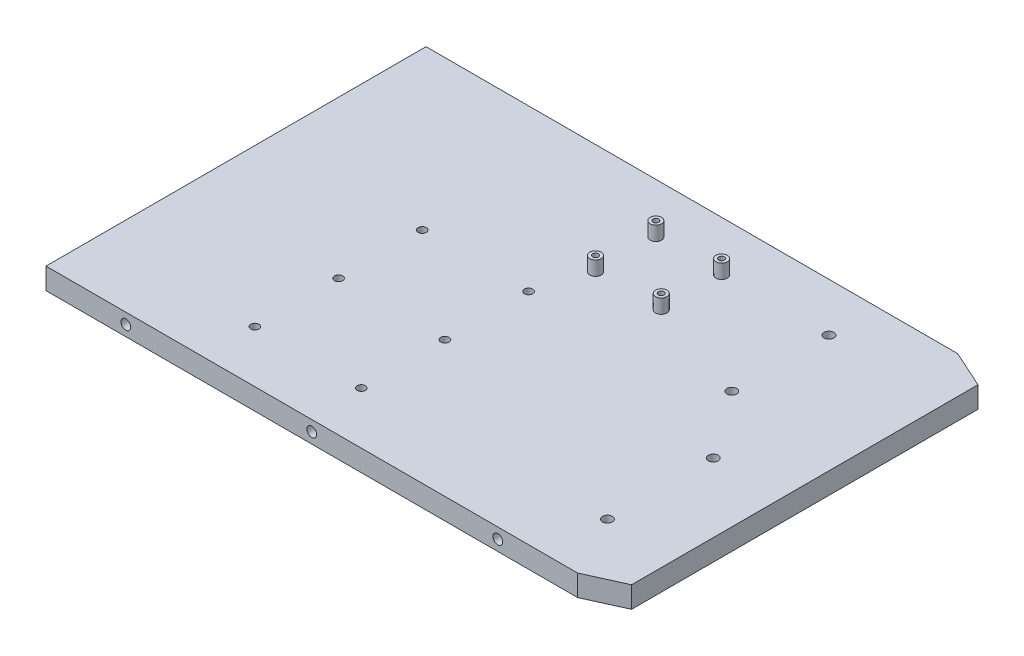
SolidWorks part; units mm, degrees
ref_plane "Front Plane" through (0, 0, 0) normal (0, 0, 1) x (1, 0, 0)
ref_plane "Top Plane" through (0, 0, 0) normal (0, 1, 0) x (1, 0, 0)
ref_plane "Right Plane" through (0, 0, 0) normal (1, 0, 0) x (0, 0, -1)
sketch "Sketch1" plane through (0, 0, 0) normal (0, 1, 0) x (1, 0, 0)
  line L2 (0, 12.0331) -> (0, 268.5969)
  line L6 (374.81, 274.2969) -> (374.81, 268.5969)
  line L9 (401.01, 18.185) -> (401.01, 262.445)
  line L10 (401.01, 262.445) -> (374.81, 274.2969)
  line L12 (374.81, 268.5969) -> (0, 268.5969)
  line L13 (0, 140.315) -> (401.01, 140.315) construction
  line L15 (401.01, 18.185) -> (374.81, 6.3331)
  line L17 (374.81, 12.0331) -> (0, 12.0331)
  line L18 (374.81, 6.3331) -> (374.81, 12.0331)
extrude "Boss-Extrude1" add sketch "Sketch1" along normal blind 10
sketch "Sketch2" plane through (0, 10, 0) normal (0, 1, 0) x (1, 0, 0)
  line L0 (0, 268.5969) -> (0, 12.0331)
  line L1 (352.4341, 121.6803) -> (352.4341, 127.0803) construction
  line L2 (0, 12.0331) -> (374.81, 12.0331)
  line L3 (352.4341, 52.4303) -> (352.4341, 47.0303) construction
  line L4 (374.81, 12.0331) -> (374.81, 6.3331)
  line L5 (374.81, 6.3331) -> (401.01, 18.185)
  line L6 (401.01, 18.185) -> (401.01, 262.445)
  line L7 (401.01, 262.445) -> (374.81, 274.2969)
  line L8 (374.81, 274.2969) -> (374.81, 268.5969)
  line L9 (374.81, 268.5969) -> (0, 268.5969)
  circle A0 centre (185.5985, 102.0168) radius 2.925
  circle A1 centre (185.5985, 161.0168) radius 2.925
  circle A2 centre (185.5985, 43.0168) radius 2.925
  circle A3 centre (110.5985, 43.0168) radius 2.925
  circle A4 centre (110.5985, 102.0168) radius 2.925
  circle A5 centre (110.5985, 161.0168) radius 2.925
  circle A8 centre (352.4341, 124.3803) radius 3.455
  circle A9 centre (352.4341, 49.7303) radius 3.455
  circle A10 centre (318.1841, 240.1847) radius 3.45
  circle A11 centre (318.1841, 171.6847) radius 3.45
  line M1 (0, 268.5969) -> (0, 12.0331)
extrude "Boss-Extrude3" add sketch "Sketch2" along normal blind 5 contours A4 A3 A0 A1 A2 A5 M1 region at (200.3556, 10, -140.3663)
sketch "Sketch3" plane through (0, 15, 0) normal (0, 1, 0) x (1, 0, 0)
  circle A0 centre (197.1863, 196.582) radius 2
  circle A1 centre (243.5413, 196.582) radius 2
  circle A2 centre (243.5413, 239.127) radius 2
  circle A3 centre (197.1863, 239.127) radius 2
  circle A4 centre (197.1863, 196.582) radius 4
  circle A5 centre (197.1863, 239.127) radius 4
  circle A6 centre (243.5413, 239.127) radius 4
  circle A8 centre (243.5413, 196.582) radius 4
extrude "Boss-Extrude4" add sketch "Sketch3" along normal blind 10
sketch "Sketch4" plane through (0, 0, -12.0331) normal (0, 0, 1) x (1, 0, 0)
  line L1 (0, 0) -> (374.81, 0)
  line L2 (0, 0) -> (0, 15)
  line L3 (0, 15) -> (374.81, 15)
  line L4 (374.81, 0) -> (374.81, 15)
  circle A0 centre (187.405, 7.5) radius 3.455
  circle A1 centre (56.2694, 7.5) radius 3.455
  circle A2 centre (318.5406, 7.5) radius 3.455
extrude "Boss-Extrude5" add sketch "Sketch4" along normal blind 5.7
sketch "Sketch5" plane through (0, 0, -268.5969) normal (0, 0, -1) x (-1, 0, 0)
  line L0 (-374.81, 0) -> (0, 0)
  line L1 (-374.81, 0) -> (-374.81, 15)
  line L2 (-374.81, 15) -> (0, 15)
  line L3 (0, 0) -> (0, 15)
  line L4 (-374.81, 15) -> (-374.81, 0) construction
  line L5 (-374.81, 15) -> (-374.81, 0) construction
  circle A0 centre (-187.405, 7.5) radius 3.455
  circle A1 centre (-318.5406, 7.5) radius 3.455
  circle A2 centre (-56.2694, 7.5) radius 3.455
extrude "Boss-Extrude6" add sketch "Sketch5" along normal blind 5.7
